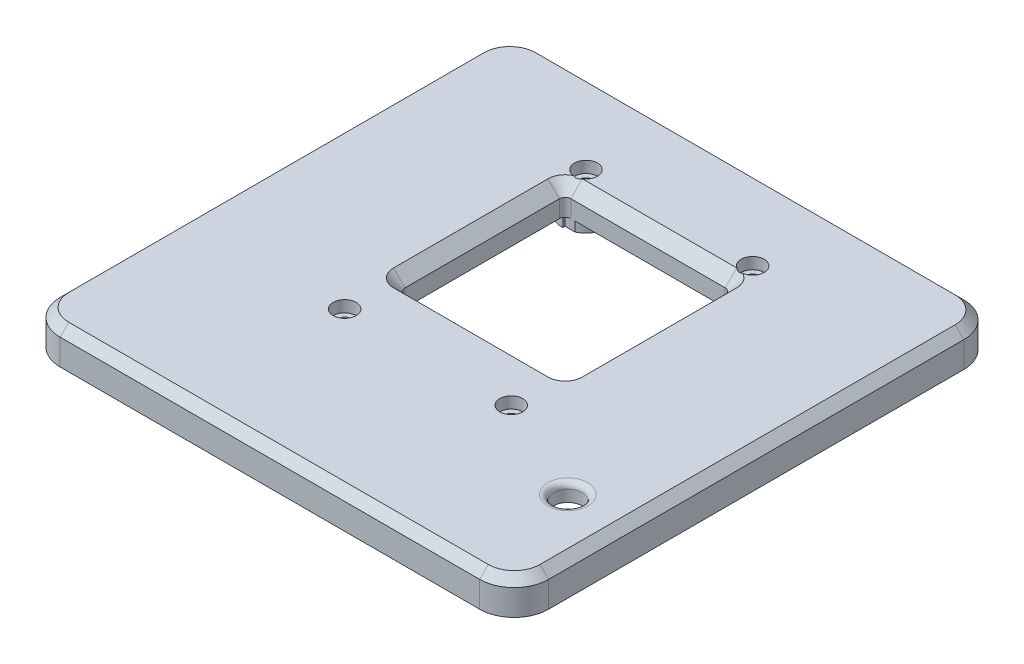
SolidWorks part; units mm, degrees
ref_plane "Front Plane" through (0, 0, 0) normal (0, 0, 1) x (1, 0, 0)
ref_plane "Top Plane" through (0, 0, 0) normal (0, 1, 0) x (1, 0, 0)
ref_plane "Right Plane" through (0, 0, 0) normal (1, 0, 0) x (0, 0, -1)
sketch "Sketch1" plane through (0, 0, 0) normal (0, 1, 0) x (1, 0, 0)
  line L0 (42.5, -42.125) -> (42.5, 42.125)
  line L1 (39.5, -39.125) -> (-39.5, -39.125)
  line L2 (39.5, -39.125) -> (39.5, 39.125)
  line L3 (39.5, 39.125) -> (-39.5, 39.125)
  line L4 (-39.5, -39.125) -> (-39.5, 39.125)
  line L5 (39.5, -39.125) -> (-39.5, 39.125) construction
  line L6 (39.5, 39.125) -> (-39.5, -39.125) construction
  line L7 (42.5, 42.125) -> (-42.5, 42.125)
  line L8 (-42.5, -42.125) -> (-42.5, 42.125)
  line L9 (42.5, -42.125) -> (-42.5, -42.125)
  point P0 (0, 0)
  dimension "D2" = 78.25
  dimension "D3" = 79
  dimension "D1" = 3
extrude "Boss-Extrude1" add sketch "Sketch1" along normal blind 3
extrude "Boss-Extrude2" add sketch "Sketch1<2>" along normal blind 3 from surface contours L9 L0 L7 L8 L1 L4 L3 L2 | L4 L1 L2 L3 region at (0, 0, 40.9282) region at (0, 0, 0) starting at face at (0, 3, 0)
sketch "Sketch1<2>" plane through (0, 0, 0) normal (0, 1, 0) x (1, 0, 0) same geometry as "Sketch1"
fillet "Fillet1" radius 3 4 edges at (39.5, 1.5, -39.125) (39.5, 1.5, 39.125) (-39.5, 1.5, -39.125) (-39.5, 1.5, 39.125)
fillet "Fillet2" radius 6 4 edges at (42.5, 3, 42.125) (42.5, 3, -42.125) (-42.5, 3, -42.125) (-42.5, 3, 42.125)
chamfer "Chamfer1" distance 1.5 angle 45 8 edges at (0, 6, -42.125) (40.7426, 6, -40.3676) (-40.7426, 6, -40.3676) (42.5, 6, 0) (-42.5, 6, 0) (40.7426, 6, 40.3676) (-40.7426, 6, 40.3676) (0, 6, 42.125)
sketch "Sketch3" plane through (0, 6, 0) normal (0, 1, 0) x (1, 0, 0)
  line L5 (-14.43, 23.68) -> (14.43, 23.68)
  line L6 (-14.43, 23.68) -> (-14.43, -5.18)
  line L7 (-14.43, -5.18) -> (14.43, -5.18)
  line L8 (14.43, 23.68) -> (14.43, -5.18)
  line L9 (-14.43, 23.68) -> (14.43, -5.18) construction
  line L10 (-14.43, -5.18) -> (14.43, 23.68) construction
  point P0 (0, 9.25)
  point P5 (0, 0)
  dimension "D1" = 28.86
  dimension "D2" = 28.86
  dimension "D3" = 9.25
extrude "Cut-Extrude1" cut sketch "Sketch3" against normal through all
fillet "Fillet3" radius 1 4 edges at (14.43, 4.5, 5.18) (-14.43, 4.5, 5.18) (-14.43, 4.5, -23.68) (14.43, 4.5, -23.68)
sketch "Sketch4" plane through (0, 3, 0) normal (0, -1, 0) x (1, 0, 0)
  line L0 (-14.43, 4.18) -> (-14.43, -22.68) construction
  line L1 (-13.43, -23.68) -> (13.43, -23.68) construction
  line L2 (14.43, -22.68) -> (14.43, 4.18) construction
  line L3 (13.43, 5.18) -> (-13.43, 5.18) construction
  line L4 (-14.43, 4.18) -> (-14.43, -22.68)
  line L5 (-13.43, -23.68) -> (13.43, -23.68)
  line L6 (14.43, -22.68) -> (14.43, 4.18)
  line L7 (13.43, 5.18) -> (-13.43, 5.18)
  line L8 (-17.43, 4.18) -> (-17.43, -22.68)
  line L9 (-13.43, -26.68) -> (13.43, -26.68)
  line L10 (17.43, -22.68) -> (17.43, 4.18)
  line L11 (13.43, 8.18) -> (-13.43, 8.18)
  arc A0 (-13.43, 5.18) -> (-14.43, 4.18) centre (-13.43, 4.18) ccw construction
  arc A1 (-14.43, -22.68) -> (-13.43, -23.68) centre (-13.43, -22.68) ccw construction
  arc A2 (13.43, -23.68) -> (14.43, -22.68) centre (13.43, -22.68) ccw construction
  arc A3 (14.43, 4.18) -> (13.43, 5.18) centre (13.43, 4.18) ccw construction
  arc A4 (-13.43, 5.18) -> (-14.43, 4.18) centre (-13.43, 4.18) ccw
  arc A5 (-14.43, -22.68) -> (-13.43, -23.68) centre (-13.43, -22.68) ccw
  arc A6 (13.43, -23.68) -> (14.43, -22.68) centre (13.43, -22.68) ccw
  arc A7 (14.43, 4.18) -> (13.43, 5.18) centre (13.43, 4.18) ccw
  arc A8 (-13.43, 8.18) -> (-17.43, 4.18) centre (-13.43, 4.18) ccw
  arc A9 (-17.43, -22.68) -> (-13.43, -26.68) centre (-13.43, -22.68) ccw
  arc A10 (13.43, -26.68) -> (17.43, -22.68) centre (13.43, -22.68) ccw
  arc A11 (17.43, 4.18) -> (13.43, 8.18) centre (13.43, 4.18) ccw
  dimension "D1" = 3
extrude "Boss-Extrude3" add sketch "Sketch4" along normal blind 2
chamfer "Chamfer2" distance 2 angle 45 8 edges at (0, 6, 5.18) (14.1371, 6, 4.8871) (-14.1371, 6, 4.8871) (14.43, 6, -9.25) (-14.43, 6, -9.25) (14.1371, 6, -23.3871) (-14.1371, 6, -23.3871) (0, 6, -23.68)
sketch "Sketch5" plane through (0, 6, 0) normal (0, 1, 0) x (1, 0, 0)
  line L1 (14.5, 27.38) -> (-14.5, 27.38) construction
  line L2 (14.5, 27.38) -> (14.5, -14.62) construction
  line L3 (14.5, -14.62) -> (-14.5, -14.62) construction
  line L4 (-14.5, 27.38) -> (-14.5, -14.62) construction
  line L5 (14.5, 27.38) -> (-14.5, -14.62) construction
  line L6 (14.5, -14.62) -> (-14.5, 27.38) construction
  circle A0 centre (-14.5, 27.38) radius 1.1
  circle A1 centre (14.5, 27.38) radius 1.1
  circle A2 centre (-14.5, -14.62) radius 1.1
  circle A3 centre (14.5, -14.62) radius 1.1
  point P0 (0, 6.38)
  dimension "D4" = 2.2
  dimension "D1" = 29
  dimension "D2" = 42
  dimension "D3" = 6.38
extrude "Cut-Extrude2" cut sketch "Sketch5" against normal through all
sketch "Sketch6" plane through (0, 3, 0) normal (0, -1, 0) x (1, 0, 0)
  line L0 (-13.43, -23.68) -> (13.43, -23.68) construction
  line L1 (-14.43, 5.18) -> (14.43, 5.18)
  line L2 (-14.43, 5.18) -> (-14.43, -23.68)
  line L3 (-14.43, -23.68) -> (14.43, -23.68)
  line L4 (14.43, 5.18) -> (14.43, -23.68)
  line L5 (-14.43, 5.18) -> (14.43, -23.68) construction
  line L6 (-14.43, -23.68) -> (14.43, 5.18) construction
  line L7 (-14.43, 4.18) -> (-14.43, -22.68) construction
  line L8 (13.43, 5.18) -> (-13.43, 5.18) construction
  arc A0 (-14.9543, -26.3782) -> (-13.6568, -26.6736) centre (-14.5, -27.38) ccw construction
  arc A1 (13.6568, -26.6736) -> (14.9543, -26.3782) centre (14.5, -27.38) ccw construction
  circle A2 centre (14.5, 14.62) radius 1.1 construction
  circle A3 centre (-14.5, 14.62) radius 1.1 construction
  circle A4 centre (-14.5, -27.38) radius 1.1
  circle A5 centre (14.5, -27.38) radius 1.1
  circle A6 centre (14.5, 14.62) radius 1.1
  circle A7 centre (-14.5, 14.62) radius 1.1
  circle A8 centre (-14.5, -27.38) radius 4.1
  circle A9 centre (14.5, -27.38) radius 4.1
  circle A10 centre (14.5, 14.62) radius 4.1
  circle A11 centre (-14.5, 14.62) radius 4.1
  arc A13 (-14.9543, -26.3782) -> (-13.6568, -26.6736) centre (-14.5, -27.38) ccw construction
  arc A14 (-16.1932, -23.646) -> (-11.3572, -24.7469) centre (-14.5, -27.38) ccw construction
  arc A15 (13.6568, -26.6736) -> (14.9543, -26.3782) centre (14.5, -27.38) ccw construction
  arc A16 (11.3572, -24.7469) -> (16.1932, -23.646) centre (14.5, -27.38) ccw construction
  point P32 (0, -9.25)
  point P40 (0, 0)
  circle M1 centre (14.5, 14.62) radius 1.1
  circle M2 centre (-14.5, 14.62) radius 1.1
  arc M3 (-13.6568, -26.6736) -> (-14.9543, -26.3782) centre (-14.5, -27.38) cw
  arc M4 (-14.9543, -26.3782) -> (-17.43, -22.68) centre (-13.43, -22.68) cw
  arc M10 (17.43, -22.68) -> (14.9543, -26.3782) centre (13.43, -22.68) cw
  arc M11 (14.9543, -26.3782) -> (13.6568, -26.6736) centre (14.5, -27.38) cw
  arc M12 (13.6568, -26.6736) -> (13.43, -26.68) centre (13.43, -22.68) cw
  line M13 (13.43, -26.68) -> (-13.43, -26.68)
  arc M14 (-13.43, -26.68) -> (-13.6568, -26.6736) centre (-13.43, -22.68) cw
  dimension "D1" = 3
extrude "Boss-Extrude4" add sketch "Sketch6" along normal blind 3.67 contours A10 M1 | A11 M2 | A8 M4 M13 M14 M3 | A8 L3 L2 A4 M13 M4 M14 | A9 L4 L3 A5 M10 M13 M12 | A9 M13 M10 M11 M12 region at (-13.7726, 3, -25.0889) region at (13.7726, 3, -25.0889) region at (-14.8427, 3, -28.4812) region at (14.8427, 3, -28.4812) region at (10.516, 3, 14.62) region at (-18.484, 3, 14.62)
sketch "Sketch7" plane through (0, 6, 0) normal (0, 1, 0) x (1, 0, 0)
  circle A0 centre (32.85, -23.13) radius 2.5
  dimension "D3" = 5
  dimension "D1" = 23.13
  dimension "D2" = 32.85
extrude "Cut-Extrude3" cut sketch "Sketch7" against normal through all
sketch "Sketch8" plane through (0, 6, 0) normal (0, 1, 0) x (1, 0, 0)
  circle A0 centre (-14.5, 27.38) radius 2
  circle A1 centre (14.5, 27.38) radius 2
  circle A2 centre (14.5, -14.62) radius 2
  circle A3 centre (-14.5, -14.62) radius 2
  dimension "D1" = 4
extrude "Cut-Extrude4" cut sketch "Sketch8" against normal blind 2
fillet "Fillet4" radius 1 1 edges at (32.85, 6, 25.63)
